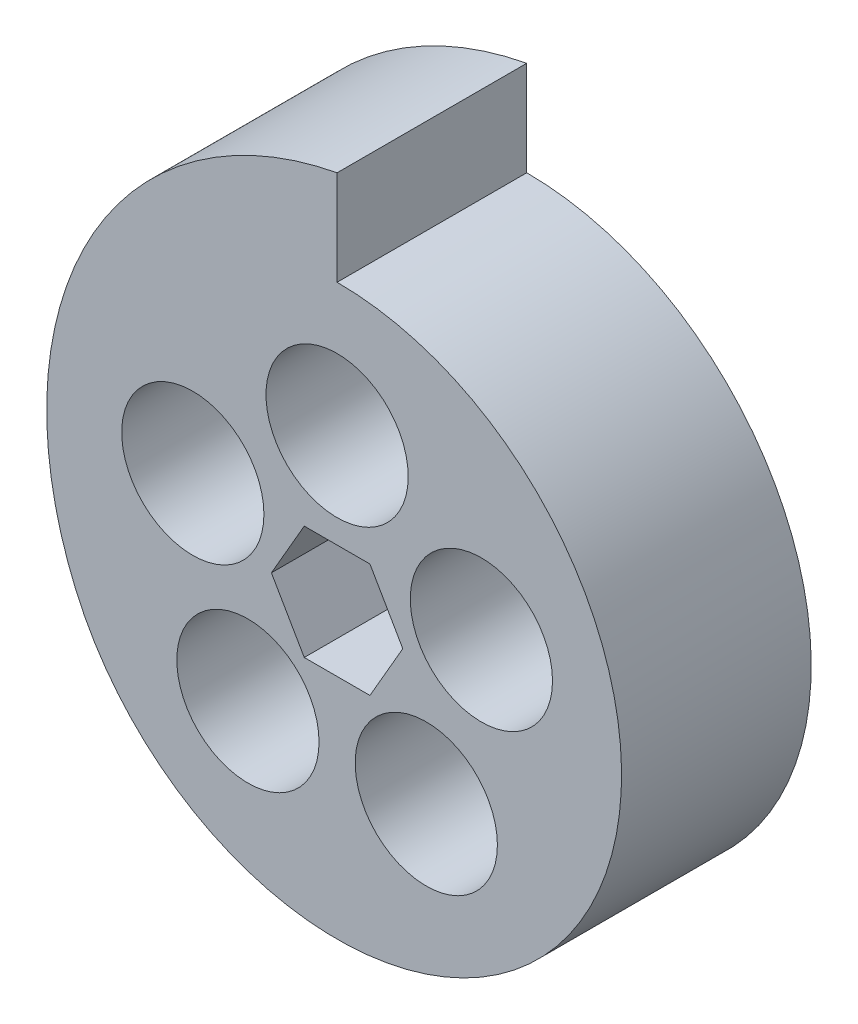
SolidWorks part; units mm, degrees
material "Commercially Pure titanium (Ti-55)  UNS R50550*"
ref_plane "Front Plane" through (0, 0, 0) normal (0, 0, 1) x (1, 0, 0)
ref_plane "Top Plane" through (0, 0, 0) normal (0, 1, 0) x (1, 0, 0)
ref_plane "Right Plane" through (0, 0, 0) normal (1, 0, 0) x (0, 0, -1)
sketch "Sketch3" plane through (0, 0, 0) normal (0, 0, 1) x (1, 0, 0)
  line L5 (0, 30) -> (0, 40)
  line L6 (6.9282, 0) -> (3.4641, 6)
  line L7 (3.4641, 6) -> (-3.4641, 6)
  line L8 (-3.4641, 6) -> (-6.9282, 0)
  line L9 (-6.9282, 0) -> (-3.4641, -6)
  line L10 (-3.4641, -6) -> (3.4641, -6)
  line L11 (3.4641, -6) -> (6.9282, 0)
  circle A2 centre (0, 0) radius 30 construction
  circle A3 centre (0, 0) radius 6 construction
  circle A4 centre (0, 16) radius 7.5
  circle A5 centre (15.2169, 4.9443) radius 7.5
  circle A6 centre (9.4046, -12.9443) radius 7.5
  circle A7 centre (-9.4046, -12.9443) radius 7.5
  circle A8 centre (-15.2169, 4.9443) radius 7.5
  arc A9 (0, 40) -> (-27.5501, -11.874) centre (7.013, 3.0226) ccw
  arc A10 (0, 30) -> (-27.5501, -11.874) centre (0, 0) cw
  point P3 (0, 0)
  point P25 (0, 0)
  dimension "D2" = 10
  dimension "D1" = 60
  dimension "D4" = 15
  dimension "D3" = 12
  dimension "D5" = 16
  dimension "D6" = 5
extrude "Boss-Extrude1" add sketch "Sketch3" along normal blind 20
